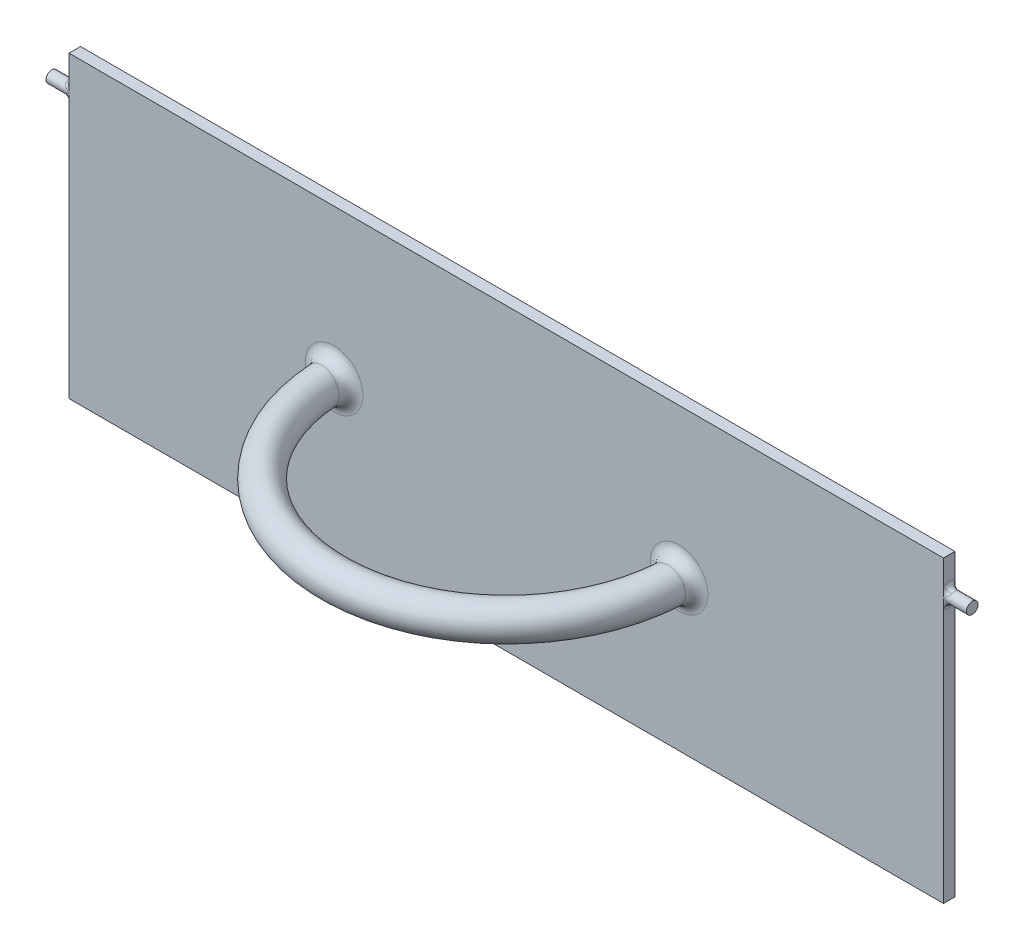
SolidWorks part; units mm, degrees
ref_plane "Plan de face" through (0, 0, 0) normal (0, 0, 1) x (1, 0, 0)
ref_plane "Plan de dessus" through (0, 0, 0) normal (0, 1, 0) x (1, 0, 0)
ref_plane "Plan de droite" through (0, 0, 0) normal (1, 0, 0) x (0, 0, -1)
sketch "Esquisse1" plane through (0, 0, 0) normal (0, 0, 1) x (1, 0, 0)
  line L1 (-190, 65) -> (190, 65)
  line L2 (-190, 65) -> (-190, -65)
  line L3 (-190, -65) -> (190, -65)
  line L4 (190, 65) -> (190, -65)
  line L5 (-190, 65) -> (190, -65) construction
  line L6 (-190, -65) -> (190, 65) construction
  point P0 (0, 0)
  dimension "D1" = 380
  dimension "D2" = 130
extrude "Boss.-Extru.1" add sketch "Esquisse1" along normal blind 5
sketch "Esquisse2" plane through (0, 0, 5) normal (0, 0, 1) x (1, 0, 0)
  line L0 (-190, 0) -> (181.9031, 0) construction
  line L1 (-190, 65) -> (-190, -65) construction
  line L2 (0, 65) -> (0, -65) construction
  line L3 (190, 65) -> (-190, 65) construction
  line L4 (-190, -65) -> (190, -65) construction
  circle A0 centre (-75, 0) radius 7.5
  circle A1 centre (75, 0) radius 7.5
  point P11 (-75, 0)
  dimension "D1" = 15
  dimension "D3" = 75
sketch "Esquisse16" plane through (0, 0, 0) normal (0, 1, 0) x (1, 0, 0)
  line L0 (-190, -5) -> (181.9031, -5) construction
  arc A0 (-75, -5) -> (75.2589, -5) centre (0.1294, -5) ccw
sweep "Balayage2" add path "Esquisse16" circular profile diameter 15 parameters "D3"=15
fillet "Congé1" radius 5 1 edges at (82.7589, 0, 5)
fillet "Congé2" radius 5 1 edges at (-67.5, 0, 5)
sketch "Esquisse23" plane through (-190, 0, 0) normal (-1, 0, 0) x (0, 0, 1)
  line L0 (0, 65) -> (0, -65) construction
  line L1 (5, 65) -> (5, -65) construction
  circle A0 centre (2.5, 50) radius 2.5
  dimension "D1" = 50
extrude "Boss.-Extru.3" add sketch "Esquisse23" along normal blind 10
mirror "Symétrie1" about plane through (0, 0, 0) normal (1, 0, 0) of "Boss.-Extru.3"
fillet "Congé3" radius 2.5 4 edges at (-190, 47.5, 2.5) (-190, 52.5, 2.5) (190, 47.5, 2.5) (190, 52.5, 2.5)
